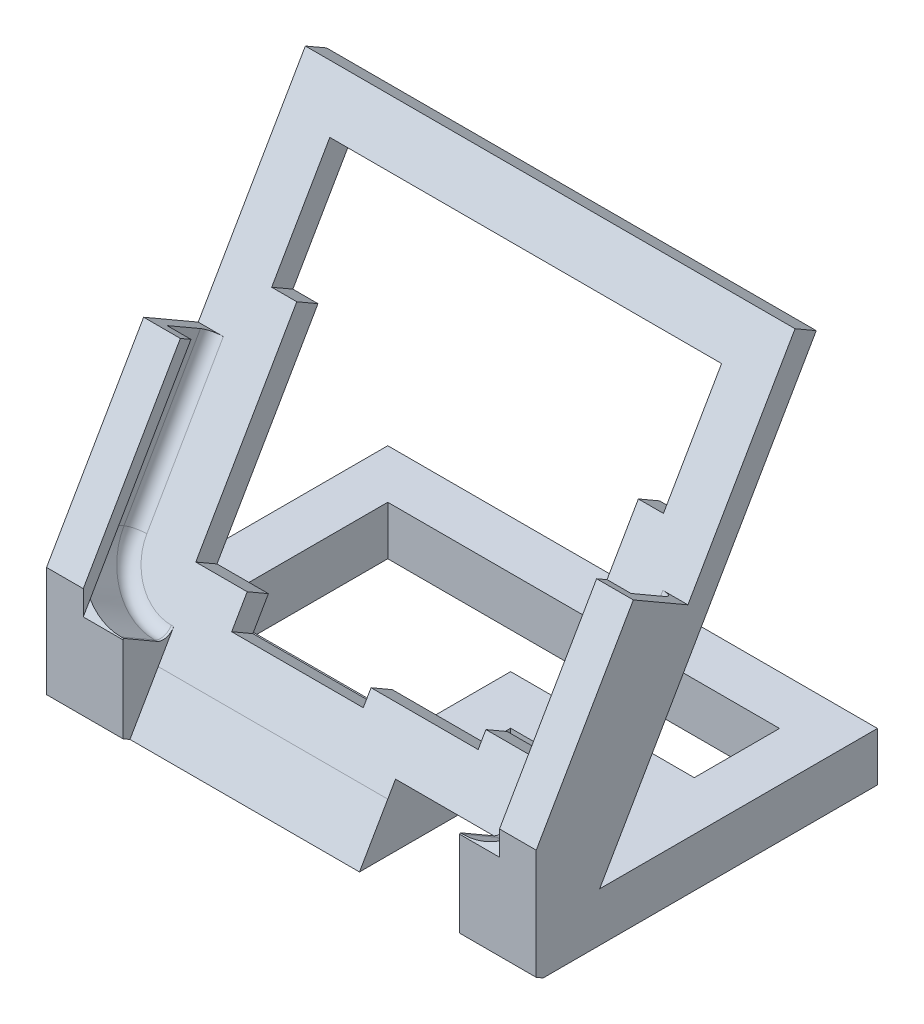
SolidWorks part; units mm, degrees
ref_plane "Front" through (0, 0, 0) normal (0, 0, 1) x (1, 0, 0)
ref_plane "Top" through (0, 0, 0) normal (0, 1, 0) x (1, 0, 0)
ref_plane "Right" through (0, 0, 0) normal (1, 0, 0) x (0, 0, -1)
sketch "Sketch1" plane through (0, 0, 0) normal (0, 1, 0) x (1, 0, 0)
  line L1 (-40, -25) -> (40, -25)
  line L2 (-40, -25) -> (-40, 25)
  line L3 (-40, 25) -> (40, 25)
  line L4 (40, -25) -> (40, 25)
  line L5 (-40, -25) -> (40, 25) construction
  line L6 (-40, 25) -> (40, -25) construction
  point P0 (0, 0)
  dimension "D1" = 80
  dimension "D2" = 50
extrude "Boss-Extrude1" add sketch "Sketch1" along normal blind 8
sketch "Sketch2" plane through (40, 0, 0) normal (1, 0, 0) x (0, 0, -1)
  line L0 (11.5359, 71.282) -> (-28.4641, 2)
  line L1 (11.5359, 71.282) -> (15, 69.282)
  line L2 (-28.4641, 2) -> (-25, 0)
  line L3 (15, 69.282) -> (-25, 0)
  line L4 (11.5359, 71.282) -> (-25, 0) construction
  line L5 (-28.4641, 2) -> (15, 69.282) construction
  line L6 (-25, 8) -> (-28.4641, 2)
  line L7 (-25, 0) -> (25, 0) construction
  line L8 (-25, 8) -> (25, 8) construction
  point P1 (-6.7321, 35.641)
  line M7 (25, 8) -> (-25, 8)
  dimension "D1" = 60
  dimension "D2" = 80
  dimension "D3" = 4
extrude "Boss-Extrude2" add sketch "Sketch2" against normal up to surface (80 mm away) contours L3 L1 L0 M7 up to face at (-40, 4, 0)
sketch "Sketch3" plane through (0, 12.8253, 22.2141) normal (0, 0.5, 0.866) x (1, 0, 0)
  line L0 (40, -2.5) -> (-40, -2.5)
  line L1 (40, 67.5) -> (40, -5.5718) construction
  line L2 (-40, -5.5718) -> (-40, 67.5) construction
  line L4 (-27.5, -2.5) -> (-27.5, -5.5718)
  line L5 (-40, -5.5718) -> (40, -5.5718) construction
  line L6 (0, -2.5) -> (0, -5.5718) construction
  line L7 (0, -5.5718) -> (-1.2175, -29.0774) construction
  line L8 (-37.9, -2.5) -> (-37.9, 32.5)
  line L9 (37.9, 32.5) -> (40, 32.5)
  line L10 (-37.9, 32.5) -> (-40, 32.5)
  line L11 (37.9, -2.5) -> (37.9, 32.5)
  line L12 (27.5, -2.5) -> (27.5, -5.5718)
  line L13 (-40, -12.5) -> (40, -12.5) construction
  line L14 (-40, -12.5) -> (40, -12.5)
  line M6 (-40, 67.5) -> (-40, -5.5718)
  line M7 (-40, -5.5718) -> (40, -5.5718)
  line M8 (40, -5.5718) -> (40, 67.5)
  dimension "D1" = 10
  dimension "D2" = 12.5
  dimension "D3" = 2.1
  dimension "D4" = 35
extrude "Boss-Extrude3" add sketch "Sketch3" along normal blind 8.3 contours L8 L10 L0 M6 | L4 L0 M6 M7 | L0 L12 M7 M8 | L11 L0 L9 M8
fillet "Fillet1" radius 10 2 edges at (-37.9, 12.7353, 27.0581) (37.9, 12.7353, 27.0581)
fillet "Fillet2" radius 2 6 edges at (27.7, 10.6603, 23.4641) (34.9711, 13.1968, 21.9996) (-27.7, 10.6603, 23.4641) (-34.9711, 13.1968, 21.9996) (37.9, 30.1458, 12.2141) (-37.9, 30.1458, 12.2141)
sketch "Sketch4" plane through (0, 0, 25) normal (0, 0, 1) x (1, 0, 0)
  line L4 (-40, 0) -> (40, 0)
  line L5 (40, 0) -> (40, 8)
  line L6 (27.5, 8) -> (-27.5, 8)
  line L7 (40, 0) -> (40, 8)
  line L8 (-40, 0) -> (40, 0)
  line L10 (27.5, 8) -> (-27.5, 8)
  line L14 (40, 8) -> (27.5, 8)
  line L15 (40, 8) -> (27.5, 8)
  line L16 (-27.5, 8) -> (-40, 8)
  line L17 (-27.5, 8) -> (-40, 8)
  line L18 (-40, 8) -> (-40, 0)
  line L19 (-40, 8) -> (-40, 0)
  dimension "D1" = 0
extrude "Boss-Extrude4" add sketch "Sketch4" along normal blind 10
chamfer "Chamfer2" distance 10 angle 60 1 edges at (0, 8, 35)
sketch "Sketch5" plane through (0, 12.8253, 22.2141) normal (0, 0.5, 0.866) x (1, 0, 0)
  line L0 (-27.5, -0.5) -> (-27.5, -5.5718) construction
  line L1 (-27.5, -0.5) -> (-27.5, -14.8094)
  line L2 (27.5, -0.5) -> (27.5, -5.5718) construction
  line L3 (27.5, -0.5) -> (27.5, -14.8094)
  line L6 (27.5, -5.5718) -> (-27.5, -5.5718)
  line L7 (-27.5, -5.5718) -> (-40, -5.5718)
  line L8 (-40, -5.5718) -> (-40, -14.8094)
  line L9 (-40, -14.8094) -> (40, -14.8094)
  line L10 (40, -14.8094) -> (40, -5.5718)
  line L11 (40, -5.5718) -> (27.5, -5.5718)
  line L12 (27.5, -5.5718) -> (-27.5, -5.5718)
  line L13 (-27.5, -5.5718) -> (-40, -5.5718)
  line L14 (-40, -5.5718) -> (-40, -14.8094)
  line L15 (-40, -14.8094) -> (40, -14.8094)
  line L16 (40, -14.8094) -> (40, -5.5718)
  line L17 (40, -5.5718) -> (27.5, -5.5718)
  line M8 (-27.5, -5.5718) -> (-40, -5.5718)
  line M9 (-40, -5.5718) -> (-40, -14.8094)
  line M10 (-40, -14.8094) -> (40, -14.8094)
  line M11 (40, -14.8094) -> (40, -5.5718)
  line M12 (40, -5.5718) -> (27.5, -5.5718)
  dimension "D1" = 0
extrude "Boss-Extrude5" add sketch "Sketch5" along normal up to surface (8.3 mm away) contours L1 M8 M9 M10 | L3 M12 M10 M11 up to face at (-34.3959, 23.6914, 25.5246)
sketch "Sketch6" plane through (0, 16.9753, 29.4021) normal (0, 0.5, 0.866) x (1, 0, 0)
  line L1 (-40, -14.8094) -> (-34, -14.8094)
  line L2 (-40, -14.8094) -> (-40, 32.5)
  line L3 (-40, 32.5) -> (-34, 32.5)
  line L4 (-34, -14.8094) -> (-34, 32.5)
  line L5 (40, -14.8094) -> (34, -14.8094)
  line L6 (-27.5, -2.5) -> (-27.9, -2.5)
  line L7 (-37.9, 7.5) -> (-37.9, 32.5)
  line L8 (-37.9, 32.5) -> (-40, 32.5)
  line L9 (-40, 32.5) -> (-40, -14.8094)
  line L10 (-40, -14.8094) -> (-27.5, -14.8094)
  line L11 (-27.5, -14.8094) -> (-27.5, -2.5)
  line L13 (-37.9, 7.5) -> (-37.9, 32.5)
  line L14 (-37.9, 32.5) -> (-40, 32.5)
  line L15 (-40, 32.5) -> (-40, -14.8094)
  line L16 (-40, -14.8094) -> (-34, -14.8094)
  line L18 (37.9, 32.5) -> (37.9, 7.5)
  line L19 (27.9, -2.5) -> (27.5, -2.5)
  line L20 (27.5, -2.5) -> (27.5, -14.8094)
  line L21 (27.5, -14.8094) -> (40, -14.8094)
  line L22 (40, -14.8094) -> (40, 32.5)
  line L23 (40, 32.5) -> (37.9, 32.5)
  line L24 (37.9, 32.5) -> (37.9, 7.5)
  line L25 (27.9, -2.5) -> (27.5, -2.5)
  line L27 (34, -14.8094) -> (40, -14.8094)
  line L28 (40, -14.8094) -> (40, 32.5)
  line L29 (40, 32.5) -> (37.9, 32.5)
  line L30 (40, -14.8094) -> (40, 32.5)
  line L31 (40, 32.5) -> (34, 32.5)
  line L32 (34, -14.8094) -> (34, 32.5)
  arc A1 (-37.9, 7.5) -> (-27.9, -2.5) centre (-27.9, 7.5) ccw
  arc A3 (27.9, -2.5) -> (37.9, 7.5) centre (27.9, 7.5) ccw
  arc A4 (27.9, -2.5) -> (37.9, 7.5) centre (27.9, 7.5) ccw
  point P12 (0, 0)
  point P15 (0, 0)
  point P21 (0, 0)
  point P22 (0, 0)
  point P23 (-28.25, -14.8094)
  point P24 (0, 0)
  dimension "D3" = 6
  dimension "D4" = 6
  dimension "D1" = 0
  dimension "D2" = 0
extrude "Boss-Extrude6" add sketch "Sketch6" along normal blind 2
chamfer "Chamfer3" distance 9 angle 60 6 edges at (30.75, 4.15, 36.8068) (-30.75, 4.15, 36.8068) (-34, 4.65, 37.6728) (-37, 5.15, 38.5389) (37, 5.15, 38.5389) (34, 4.65, 37.6728)
sketch "Sketch7" plane through (0, 12.8253, 22.2141) normal (0, 0.5, 0.866) x (1, 0, 0)
  line L0 (27.5, -3.0359) -> (27.5, -14.8094) construction
  line L1 (27.5, -0.5) -> (27.5, -5.5718) construction
  line L2 (27.5, -14.8094) -> (27.5, -8.9226) construction
  line L3 (27.5, -8.9226) -> (-25.3393, -8.9226) construction
  line L4 (27.5, -14.8094) -> (-27.5, -14.8094) construction
  line L5 (27.5, -3.0359) -> (10, -3.0359)
  line L6 (27.5, -3.0359) -> (27.5, -14.8094)
  line L7 (27.5, -14.8094) -> (10, -14.8094)
  line L8 (10, -3.0359) -> (10, -14.8094)
  dimension "D1" = 17.5
extrude "Cut-Extrude1" cut sketch "Sketch7" against normal blind 12
sketch "Sketch8" plane through (0, 8, 0) normal (0, 1, 0) x (1, 0, 0)
  line L0 (10, -20.3812) -> (10, -19.9282) construction
  line L1 (27.5, -19.9282) -> (10, -19.9282)
  line L2 (27.5, -19.9282) -> (27.5, -4.9282)
  line L3 (27.5, -4.9282) -> (10, -4.9282)
  line L4 (10, -19.9282) -> (10, -4.9282)
  dimension "D1" = 15
extrude "Cut-Extrude2" cut sketch "Sketch8" against normal blind 12
sketch "Sketch9" plane through (0, 8, 0) normal (0, 1, 0) x (1, 0, 0)
  line L0 (2, 3.0718) -> (32, 3.0718)
  line L1 (32, 3.0718) -> (32, 3.0718)
  line L2 (32, 3.0718) -> (32, 3.0718)
  line L3 (32, 3.0718) -> (32, 17)
  line L4 (32, 17) -> (-32, 17)
  line L5 (-32, 17) -> (-32, -12.3812)
  line L6 (-32, -12.3812) -> (2, -12.3812)
  line L7 (2, -12.3812) -> (2, 3.0718)
  line L8 (10, -4.9282) -> (27.5, -4.9282)
  line L9 (27.5, -4.9282) -> (27.5, -20.3812)
  line L10 (27.5, -20.3812) -> (40, -20.3812)
  line L11 (40, -20.3812) -> (40, 25)
  line L12 (40, 25) -> (-40, 25)
  line L13 (-40, 25) -> (-40, -20.3812)
  line L14 (-40, -20.3812) -> (10, -20.3812)
  line L15 (10, -20.3812) -> (10, -4.9282)
  line L16 (10, -4.9282) -> (27.5, -4.9282)
  line L17 (27.5, -4.9282) -> (27.5, -20.3812)
  line L18 (27.5, -20.3812) -> (40, -20.3812)
  line L19 (40, -20.3812) -> (40, 25)
  line L20 (40, 25) -> (-40, 25)
  line L21 (-40, 25) -> (-40, -20.3812)
  line L22 (-40, -20.3812) -> (10, -20.3812)
  line L23 (10, -20.3812) -> (10, -4.9282)
  dimension "D1" = 0
  dimension "D2" = 8
extrude "Cut-Extrude3" cut sketch "Sketch9" against normal blind 12 contours L6 L7 L0 L3 L4 L5
sketch "Sketch10" plane through (0, 12.8253, 22.2141) normal (0, 0.5, 0.866) x (1, 0, 0)
  line L0 (2, 2.4282) -> (2, 4.9641)
  line L1 (2, 4.9641) -> (19.5, 4.9641)
  line L2 (19.5, 4.9641) -> (19.5, 7.5)
  line L3 (19.5, 7.5) -> (27.9, 7.5)
  line L4 (27.9, 7.5) -> (27.9, 40.5)
  line L5 (27.9, 40.5) -> (32, 40.5)
  line L6 (32, 40.5) -> (32, 59.5)
  line L7 (32, 59.5) -> (-32, 59.5)
  line L8 (-32, 59.5) -> (-32, 40.5)
  line L9 (-32, 40.5) -> (-27.9, 40.5)
  line L10 (-27.9, 40.5) -> (-27.9, 7.5)
  line L11 (-27.9, 7.5) -> (-19.5, 7.5)
  line L12 (-19.5, 7.5) -> (-19.5, 2.4282)
  line L13 (-19.5, 2.4282) -> (2, 2.4282)
  line L14 (10, -5.5718) -> (10, -3.0359)
  line L15 (10, -3.0359) -> (27.5, -3.0359)
  line L16 (27.5, -3.0359) -> (27.5, -0.5)
  line L17 (27.5, -0.5) -> (27.9, -0.5)
  line L18 (35.9, 7.5) -> (35.9, 32.5)
  line L19 (35.9, 32.5) -> (40, 32.5)
  line L20 (40, 32.5) -> (40, 67.5)
  line L21 (40, 67.5) -> (-40, 67.5)
  line L22 (-40, 67.5) -> (-40, 32.5)
  line L23 (-40, 32.5) -> (-35.9, 32.5)
  line L24 (-35.9, 32.5) -> (-35.9, 7.5)
  line L25 (-27.9, -0.5) -> (-27.5, -0.5)
  line L26 (-27.5, -0.5) -> (-27.5, -5.5718)
  line L27 (-27.5, -5.5718) -> (10, -5.5718)
  line L28 (10, -5.5718) -> (10, -3.0359)
  line L29 (10, -3.0359) -> (27.5, -3.0359)
  line L30 (27.5, -3.0359) -> (27.5, -0.5)
  line L31 (27.5, -0.5) -> (27.9, -0.5)
  line L32 (35.9, 7.5) -> (35.9, 32.5)
  line L33 (35.9, 32.5) -> (40, 32.5)
  line L34 (40, 32.5) -> (40, 67.5)
  line L35 (40, 67.5) -> (-40, 67.5)
  line L36 (-40, 67.5) -> (-40, 32.5)
  line L37 (-40, 32.5) -> (-35.9, 32.5)
  line L38 (-35.9, 32.5) -> (-35.9, 7.5)
  line L39 (-27.9, -0.5) -> (-27.5, -0.5)
  line L40 (-27.5, -0.5) -> (-27.5, -5.5718)
  line L41 (-27.5, -5.5718) -> (10, -5.5718)
  arc A0 (27.9, 7.5) -> (27.9, 7.5) centre (27.9, 7.5) ccw
  arc A1 (-27.9, 7.5) -> (-27.9, 7.5) centre (-27.9, 7.5) ccw
  arc A2 (27.9, -0.5) -> (35.9, 7.5) centre (27.9, 7.5) ccw
  arc A3 (-35.9, 7.5) -> (-27.9, -0.5) centre (-27.9, 7.5) ccw
  arc A4 (27.9, -0.5) -> (35.9, 7.5) centre (27.9, 7.5) ccw
  arc A5 (-35.9, 7.5) -> (-27.9, -0.5) centre (-27.9, 7.5) ccw
  dimension "D1" = 0
  dimension "D2" = 8
extrude "Cut-Extrude4" cut sketch "Sketch10" against normal up to surface (4 mm away) contours L12 L13 L0 L1 L2 L3 L4 L5 L6 L7 L8 L9 L10 L11 up to face at (9.375, 23.3695, 11.5076)
